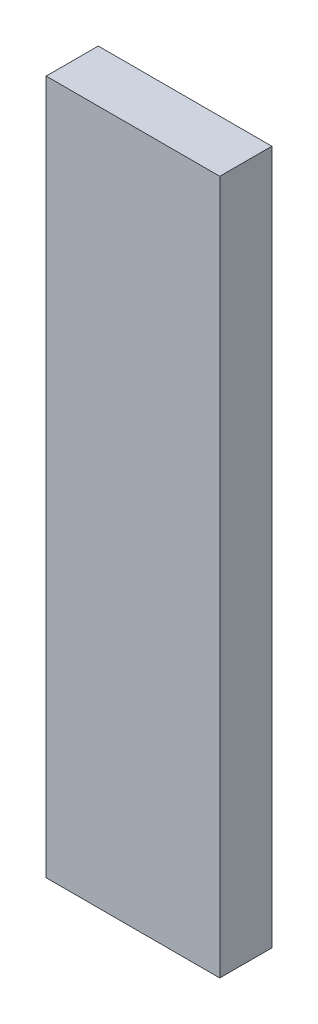
SolidWorks part; units mm, degrees
material "Acrylic (Medium-high impact)"
ref_plane "Front Plane" through (0, 0, 0) normal (0, 0, 1) x (1, 0, 0)
ref_plane "Top Plane" through (0, 0, 0) normal (0, 1, 0) x (1, 0, 0)
ref_plane "Right Plane" through (0, 0, 0) normal (1, 0, 0) x (0, 0, -1)
sketch "Sketch1" plane through (0, 0, 0) normal (0, 0, 1) x (1, 0, 0)
  line L0 (7.5, 0) -> (-7.5, 0)
  line L1 (55, 0) -> (-55, 0) construction
  line L2 (-7.5, 0) -> (-7.5, 60)
  line L3 (-7.5, 60) -> (0, 60)
  line L6 (0, -55) -> (0, 55) construction
  line L8 (7.5, 60) -> (0, 60)
  line L9 (7.5, 0) -> (7.5, 60)
  point P0 (0, 60)
  point P12 (0, 66)
  point P15 (0, 0)
  dimension "D1" = 7.5
  dimension "D4" = 60
extrude "Boss-Extrude1" add sketch "Sketch1" along normal blind 4.5
